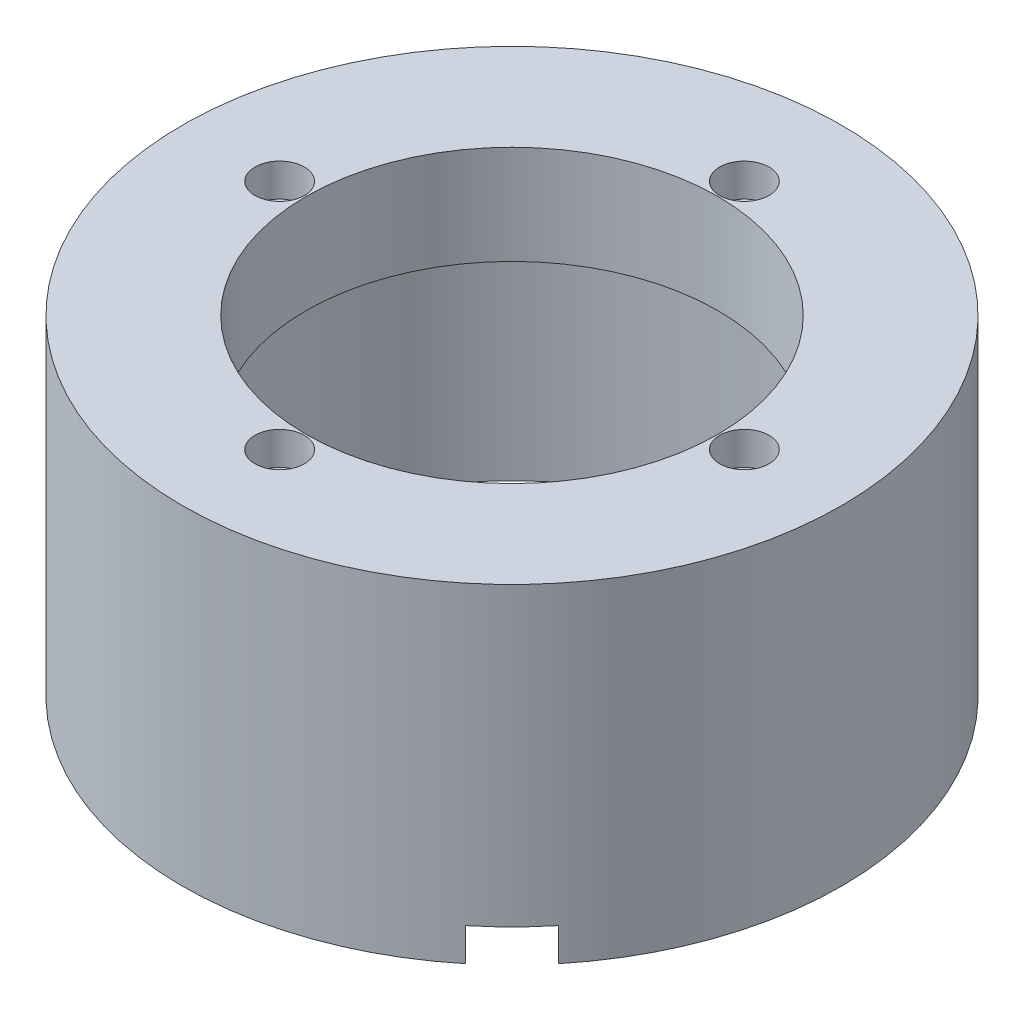
SolidWorks part; units mm, degrees
ref_plane "Alzado" through (0, 0, 0) normal (0, 0, 1) x (1, 0, 0)
ref_plane "Planta" through (0, 0, 0) normal (0, 1, 0) x (1, 0, 0)
ref_plane "Vista lateral" through (0, 0, 0) normal (1, 0, 0) x (0, 0, -1)
sketch "Croquis1" plane through (0, 0, 0) normal (0, 1, 0) x (1, 0, 0)
  circle A0 centre (0, 0) radius 50
  circle A1 centre (0, 0) radius 31.25
  dimension "D1" = 62.5
  dimension "D2" = 100
extrude "Saliente-Extruir1" add sketch "Croquis1" along normal blind 50
sketch "Croquis2" plane through (0, 0, 0) normal (0, -1, 0) x (1, 0, 0)
  circle A0 centre (0, 0) radius 40
  dimension "D1" = 80
extrude "Cortar-Extruir1" cut sketch "Croquis2" against normal blind 35
sketch "Croquis3" plane through (0, 0, 0) normal (0, -1, 0) x (1, 0, 0)
  line L0 (0, 0) -> (0, 50) construction
  circle A0 centre (0, 0) radius 50 construction
  circle A1 centre (0, 45) radius 1.5
  circle A2 centre (0, 35.25) radius 2
  circle A3 centre (45, 0) radius 1.5
  circle A4 centre (35.25, 0) radius 2
  circle A5 centre (0, -45) radius 1.5
  circle A6 centre (0, -35.25) radius 2
  circle A7 centre (-45, 0) radius 1.5
  circle A8 centre (-35.25, 0) radius 2
  point P25 (0, 0)
  dimension "D3" = 4
  dimension "D4" = 3
  dimension "D1" = 45
  dimension "D2" = 35.25
  dimension "D5" = 4
extrude "Cortar-Extruir2" cut sketch "Croquis3" against normal blind 35 contours A5 | L0 A1 | A1 L0 | A7 | A3 region at (-0.6366, 0, 45) region at (0.6366, 0, 45) region at (0, 0, -45)
extrude "Cortar-Extruir3" cut sketch "Croquis3<3>" against normal through all contours L0 A2 | A2 L0 | A4 | A6 | A8 region at (-0.8488, 0, 35.25) region at (0.8488, 0, 35.25) region at (35.25, 0, 0) region at (0, 0, -35.25) region at (-35.25, 0, 0)
sketch "Croquis3<3>" plane through (0, 0, 0) normal (0, -1, 0) x (1, 0, 0) same geometry as "Croquis3"
sketch "Croquis4" plane through (0, 50, 0) normal (0, 1, 0) x (1, 0, 0)
  circle A0 centre (0, 35.25) radius 3.75
  circle A1 centre (35.25, 0) radius 3.75
  circle A2 centre (0, -35.25) radius 3.75
  circle A3 centre (-35.25, 0) radius 3.75
  point P12 (0, 0)
  dimension "D1" = 7.5
  dimension "D2" = 4
extrude "Cortar-Extruir4" cut sketch "Croquis4" against normal blind 5
sketch "Croquis8" plane through (0, 0, 0) normal (0, -1, 0) x (1, 0, 0)
  line L0 (0, 0) -> (50, 0) construction
  line L1 (0, 0) -> (35.3553, 35.3553) construction
  line L2 (35.3553, 35.3553) -> (25.2148, 25.2148)
  line L3 (35.3553, 35.3553) -> (38.8909, 31.8198)
  line L4 (25.2148, 25.2148) -> (28.7504, 21.6793)
  line L5 (38.8909, 31.8198) -> (28.7504, 21.6793)
  line L6 (35.3553, 35.3553) -> (25.2148, 25.2148)
  line L7 (35.3553, 35.3553) -> (31.8198, 38.8909)
  line L8 (25.2148, 25.2148) -> (21.6793, 28.7504)
  line L9 (31.8198, 38.8909) -> (21.6793, 28.7504)
  circle A0 centre (0, 0) radius 50 construction
  circle M9 centre (0, 0) radius 40
  circle M10 centre (0, 0) radius 50
  dimension "D1" = 45
  dimension "D2" = 5
  dimension "D3" = 5
extrude "Cortar-Extruir5" cut sketch "Croquis8" against normal blind 5 contours L9 L2 M10 M9 | L5 L2 M10 M9 region at (33.5229, 0, 29.9837) region at (29.9837, 0, 33.5229)
